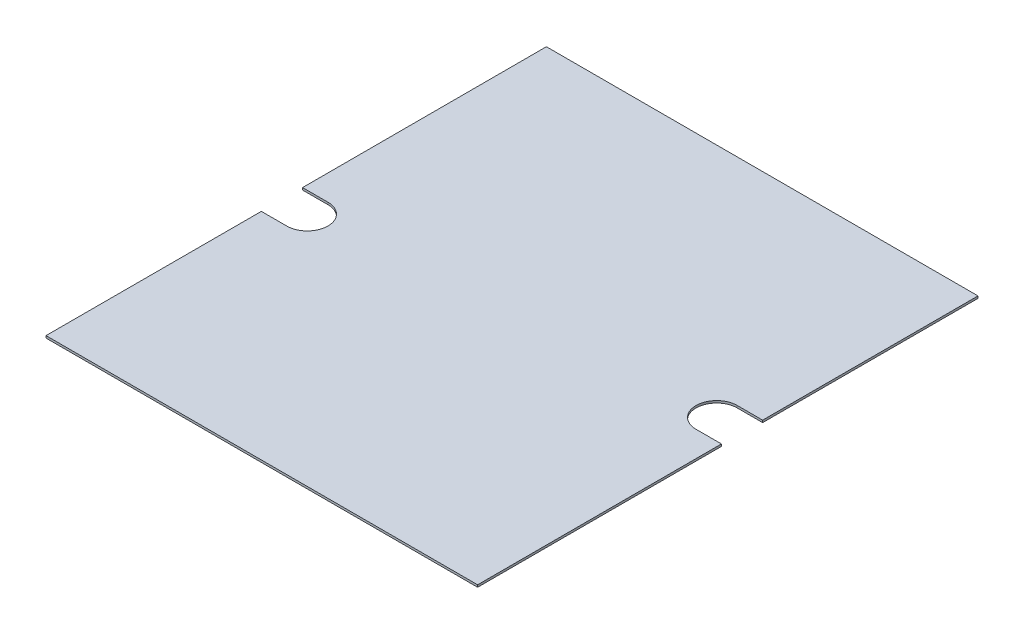
SolidWorks part; units mm, degrees
ref_plane "Front Plane" through (0, 0, 0) normal (0, 0, 1) x (1, 0, 0)
ref_plane "Top Plane" through (0, 0, 0) normal (0, 1, 0) x (1, 0, 0)
ref_plane "Right Plane" through (0, 0, 0) normal (1, 0, 0) x (0, 0, -1)
sketch "Sketch1" plane through (0, 0, 0) normal (0, 1, 0) x (1, 0, 0)
  line L1 (0, 0) -> (199, 0)
  line L3 (0, 230.7) -> (199, 230.7)
  line L5 (11.75, 118.25) -> (0.0406, 118.25)
  line L6 (11.75, 99.25) -> (0.0406, 99.25)
  line L8 (0.0406, 118.25) -> (0, 230.7)
  line L9 (0.0406, 99.25) -> (0, 0)
  line L10 (99.5, 230.7) -> (99.5, 0) construction
  line L11 (187.25, 99.25) -> (198.9594, 99.25) construction
  line L12 (187.25, 118.25) -> (198.9594, 118.25) construction
  line L13 (199, 115.35) -> (0.0406, 115.35) construction
  line L14 (187.25, 131.45) -> (198.9594, 131.45)
  line L15 (187.25, 112.45) -> (198.9594, 112.45)
  line L16 (199, 230.7) -> (198.9594, 131.45)
  line L17 (198.9594, 112.45) -> (199, 0)
  arc A1 (11.75, 99.25) -> (11.75, 118.25) centre (11.75, 108.75) ccw
  arc A2 (187.25, 99.25) -> (187.25, 118.25) centre (187.25, 108.75) cw construction
  arc A3 (187.25, 131.45) -> (187.25, 112.45) centre (187.25, 121.95) ccw
  dimension "D4" = 19
  dimension "D1" = 199
  dimension "D2" = 230.7
  dimension "D5" = 108.75
extrude "Boss-Extrude1" add sketch "Sketch1" along normal blind 1
